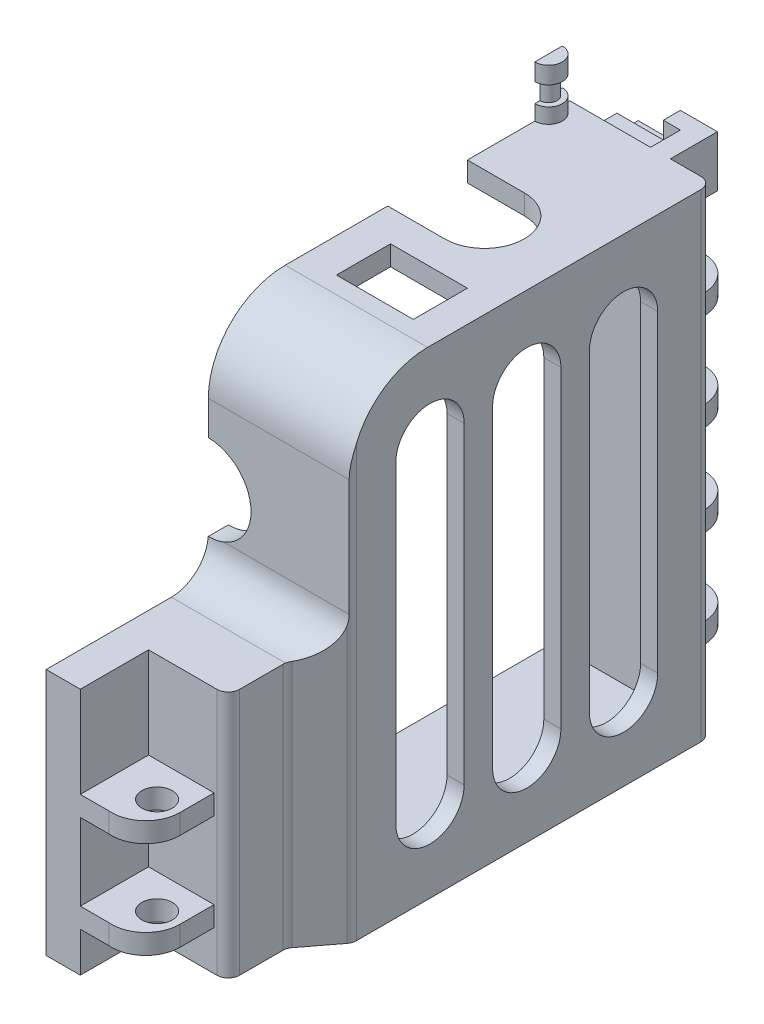
SolidWorks part; units mm, degrees
other "Marca1"
sketch "Croquis36" plane through (80, 81, -87.96) normal (0.1619, 0.9849, -0.0617) x (0.0148, -0.0649, -0.9978)
ref_plane "Front Plane" through (0, 0, 0) normal (0, 0, 1) x (1, 0, 0)
ref_plane "Top Plane" through (0, 0, 0) normal (0, 1, 0) x (1, 0, 0)
ref_plane "Right Plane" through (0, 0, 0) normal (1, 0, 0) x (0, 0, -1)
sketch "Croquis13" plane through (0, 0, 0) normal (0, 1, 0) x (1, 0, 0)
  line L0 (0, 80) -> (23, 80)
  line L1 (25, 78) -> (25, 17.5)
  line L2 (24.5908, 16.2879) -> (20.4092, 10.7997)
  line L3 (20, 9.5876) -> (20, 2)
  line L4 (18, 0) -> (0, 0)
  line L5 (0, 77) -> (22, 77)
  line L6 (22, 77) -> (22, 17.8376)
  line L7 (22, 17.8376) -> (18.0229, 12.6179)
  line L8 (17, 9.5876) -> (17, 3)
  line L9 (17, 3) -> (0, 3)
  line L10 (0, 80) -> (0, 77)
  line L11 (0, 3) -> (0, 0)
  line L12 (0, 77) -> (0, 3)
  line L13 (22, 20) -> (25, 20)
  arc A0 (20, 2) -> (18, 0) centre (18, 2) cw
  arc A1 (20.4092, 10.7997) -> (20, 9.5876) centre (22, 9.5876) ccw
  arc A2 (25, 17.5) -> (24.5908, 16.2879) centre (23, 17.5) cw
  arc A3 (23, 80) -> (25, 78) centre (23, 78) cw
  arc A4 (22, 77) -> (22, 77) centre (22, 77) cw
  arc A5 (22, 17.8376) -> (22, 17.8376) centre (22, 17.8376) cw
  arc A6 (18.0229, 12.6179) -> (17, 9.5876) centre (22, 9.5876) ccw
  arc A7 (17, 3) -> (17, 3) centre (17, 3) cw
  dimension "D1" = 2
  dimension "D2" = 80
  dimension "D3" = 25
  dimension "D4" = 60
  dimension "D5" = 8.25
  dimension "D6" = 20
  dimension "D8" = 2.5
  dimension "D7" = 3
extrude "Saliente-Extruir1" add sketch "Croquis13" along normal blind 3 contours A7 L8 A6 L7 A5 L6 A4 L5 L12 L9 region at (10.6798, 0, -41.1375)
extrude "Saliente-Extruir2" add sketch "Croquis13<3>" along normal blind 80.5 contours L5 A4 L6 L13 L1 A3 L0 L10 region at (11.5, 0, -79.35)
sketch "Croquis13<3>" plane through (0, 0, 0) normal (0, 1, 0) x (1, 0, 0) same geometry as "Croquis13"
extrude "Saliente-Extruir3" add sketch "Croquis13<4>" along normal blind 40 contours L8 A7 L9 L11 L4 A0 L3 A1 L2 A2 L1 L13 L6 A5 L7 A6 region at (8.5, 0, -2.6798)
sketch "Croquis13<4>" plane through (0, 0, 0) normal (0, 1, 0) x (1, 0, 0) same geometry as "Croquis13"
fillet "Redondeo1" radius 10 2 edges at (23.5, 80.5, -20) (23.5, 40, -20)
sketch "Croquis14" plane through (0, 0, 0) normal (1, 0, 0) x (0, 0, -1)
  line L2 (2, 40) -> (0, 40) construction
  line L43 (2, 40) -> (0, 40)
  line L44 (9.5876, 40) -> (2, 40) construction
  line L45 (9.5876, 40) -> (2, 40)
  line L46 (20, 70.5) -> (20, 50) construction
  line L47 (10, 40) -> (9.5876, 40) construction
  line L48 (20, 70.5) -> (20, 50)
  line L49 (10, 40) -> (9.5876, 40)
  line L50 (78, 80.5) -> (30, 80.5) construction
  line L51 (78, 80.5) -> (30, 80.5)
  line L52 (80, 80.5) -> (78, 80.5) construction
  line L53 (80, 80.5) -> (78, 80.5)
  line L54 (80, 84) -> (78, 84)
  line L55 (78, 84) -> (30, 84)
  line L56 (16.5, 70.5) -> (16.5, 50)
  line L57 (10, 43.5) -> (9.5876, 43.5)
  line L58 (9.5876, 43.5) -> (2, 43.5)
  line L59 (2, 43.5) -> (0, 43.5)
  line L60 (0, 43.5) -> (0, 40)
  line L61 (80, 84) -> (80, 80.5)
  arc A24 (17.5, 43.3856) -> (20, 50) centre (10, 50) ccw construction
  arc A25 (16.2879, 42.2242) -> (17.5, 43.3856) centre (10, 50) ccw construction
  arc A26 (10.7997, 40.032) -> (16.2879, 42.2242) centre (10, 50) ccw construction
  arc A27 (10, 40) -> (10.7997, 40.032) centre (10, 50) ccw construction
  arc A28 (17.5, 43.3856) -> (20, 50) centre (10, 50) ccw
  arc A29 (16.2879, 42.2242) -> (17.5, 43.3856) centre (10, 50) ccw
  arc A30 (10.7997, 40.032) -> (16.2879, 42.2242) centre (10, 50) ccw
  arc A31 (10, 40) -> (10.7997, 40.032) centre (10, 50) ccw
  arc A32 (30, 80.5) -> (20, 70.5) centre (30, 70.5) ccw construction
  arc A33 (30, 80.5) -> (20, 70.5) centre (30, 70.5) ccw
  arc A34 (30, 84) -> (16.5, 70.5) centre (30, 70.5) ccw
  arc A35 (14.875, 45.7007) -> (16.5, 50) centre (10, 50) ccw
  arc A36 (14.0871, 44.9458) -> (14.875, 45.7007) centre (10, 50) ccw
  arc A37 (10.5198, 43.5208) -> (14.0871, 44.9458) centre (10, 50) ccw
  arc A38 (10, 43.5) -> (10.5198, 43.5208) centre (10, 50) ccw
  dimension "D1" = 3.5
extrude "Saliente-Extruir4" add sketch "Croquis14" along normal up to surface (25 mm away) up to face at (25, 46.6755, -37.0762)
sketch "Croquis16" plane through (0, 0, 0) normal (1, 0, 0) x (0, 0, -1)
  line L0 (77, 3) -> (61.19, 3) construction
  line L1 (77, 3) -> (3, 3) construction
  line L2 (61.19, 3) -> (56.19, 3) construction
  line L3 (58.69, 3) -> (58.69, 19) construction
  line L4 (61.19, 3) -> (78.15, 3)
  line L5 (61.19, 3) -> (61.19, 19)
  line L6 (61.19, 19) -> (78.15, 19)
  line L7 (78.15, 3) -> (78.15, 19)
  line L8 (61.19, 19) -> (58.69, 19) construction
  line L9 (56.19, 3) -> (53.19, 3)
  line L12 (56.19, 3) -> (56.19, 19)
  line L13 (56.19, 19) -> (56.19, 80.5)
  line L15 (56.19, 19) -> (56.19, 3)
  line L16 (56.19, 3) -> (53.19, 3)
  line L17 (53.19, 80.5) -> (53.19, 3)
  line L18 (30, 80.5) -> (77, 80.5) construction
  line L19 (56.19, 80.5) -> (53.19, 80.5)
  dimension "D1" = 15.81
  dimension "D2" = 5
  dimension "D3" = 16.96
  dimension "D4" = 16
  dimension "D5" = 3
extrude "Saliente-Extruir5" add sketch "Croquis16" along normal up to surface (22 mm away) region at (0, 41.75, -54.69)
sketch "Croquis18" plane through (0, 0, 0) normal (1, 0, 0) x (0, 0, -1)
  line L34 (45.7, 80.5) -> (42.4, 80.5)
  line L35 (45.7, 80.5) -> (45.7, 29.9)
  line L36 (42.4, 68.7) -> (42.4, 36.7)
  line L37 (36.9, 68.7) -> (36.9, 65.5)
  line L38 (77, 80.5) -> (73.7, 80.5)
  line L39 (33.9, 29.9) -> (33.9, 39.9)
  line L40 (42.4, 36.7) -> (36.9, 36.7)
  line L41 (36.9, 36.7) -> (36.9, 39.9)
  line L42 (36.9, 39.9) -> (33.9, 39.9)
  line L43 (36.9, 65.5) -> (33.9, 65.5)
  line L44 (33.9, 65.5) -> (33.9, 80.5)
  line L45 (33.9, 80.5) -> (42.4, 80.5)
  line L46 (36.9, 68.7) -> (42.4, 68.7)
  line L47 (33.9, 29.9) -> (45.7, 29.9)
  line L48 (77, 80.5) -> (77, 29.9)
  line L49 (73.7, 68.7) -> (73.7, 36.7)
  line L50 (68.2, 68.7) -> (68.2, 65.5)
  line L51 (65.2, 29.9) -> (65.2, 39.9)
  line L52 (73.7, 36.7) -> (68.2, 36.7)
  line L53 (68.2, 36.7) -> (68.2, 39.9)
  line L54 (68.2, 39.9) -> (65.2, 39.9)
  line L55 (68.2, 65.5) -> (65.2, 65.5)
  line L56 (65.2, 65.5) -> (65.2, 80.5)
  line L57 (65.2, 80.5) -> (73.7, 80.5)
  line L58 (68.2, 68.7) -> (73.7, 68.7)
  line L59 (65.2, 29.9) -> (77, 29.9)
  line L61 (30, 80.5) -> (53.19, 80.5) construction
  line L62 (77, 80.5) -> (77, 3) construction
  dimension "D1" = 3.3
  dimension "D2" = 10
  dimension "D3" = 5.5
  dimension "D4" = 3.2
  dimension "D5" = 32
  dimension "D6" = 15
  dimension "D7" = 3.3
  dimension "D8" = 3
  dimension "D9" = 5.5
  dimension "D10" = 15
  dimension "D11" = 3.3
  dimension "D13" = 28
sketch "Croquis27" plane through (0, 0, -20) normal (0, 0, 1) x (1, 0, 0)
  circle A0 centre (0, 57) radius 7.5
  dimension "D1" = 57
  dimension "D2" = 15
extrude "Cortar-Extruir4" cut sketch "Croquis27" against normal blind 10 and the other way through all
sketch "Croquis29" plane through (0, 0, 0) normal (-1, 0, 0) x (0, 0, 1)
  line L0 (-53.19, 80.5) -> (-53.19, 3) construction
  line L1 (-56.19, 3) -> (-56.19, 80.5) construction
  line L2 (-53.19, 80.5) -> (-53.19, 3)
  line L3 (-56.19, 3) -> (-56.19, 80.5)
  line L4 (-56.19, 80.5) -> (-53.19, 80.5)
  line L5 (-56.19, 3) -> (-53.19, 3)
extrude "Cortar-Extruir5" cut sketch "Croquis29" against normal up to surface (22 mm away) up to face at (22, 41.75, -66.595)
sketch "Croquis37" plane through (0, 40, 0) normal (0, -1, 0) x (1, 0, 0)
  line L2 (23, -80) -> (25, -80)
  line L3 (20.4092, -10.7997) -> (24.5908, -16.2879)
  line L4 (25, -17.5) -> (25, -10)
  line L5 (25, -10) -> (20.043, -10)
  line L6 (20.4092, -10.7997) -> (24.5908, -16.2879)
  line L7 (25, -17.5) -> (25, -10)
  line L8 (25, -10) -> (20.043, -10)
  line L9 (25, -80) -> (25, -78)
  line L10 (20, -2) -> (20, -9.5876)
  line L11 (20.043, -10) -> (25, -10)
  line L12 (25, -10) -> (25, 0)
  line L13 (25, 0) -> (18, 0)
  line L14 (20, -2) -> (20, -9.5876)
  line L15 (20.043, -10) -> (25, -10)
  line L16 (25, -10) -> (25, 0)
  line L19 (23, -80) -> (25, -80)
  line L20 (25, -80) -> (25, -78)
  line L23 (25, 0) -> (18, 0)
  arc A1 (23, -80) -> (25, -78) centre (23, -78) ccw
  arc A2 (20.043, -10) -> (20.4092, -10.7997) centre (22, -9.5876) ccw
  arc A3 (25, -17.5) -> (24.5908, -16.2879) centre (23, -17.5) ccw
  arc A4 (20.043, -10) -> (20.4092, -10.7997) centre (22, -9.5876) ccw
  arc A5 (25, -17.5) -> (24.5908, -16.2879) centre (23, -17.5) ccw
  arc A6 (20, -2) -> (18, 0) centre (18, -2) ccw
  arc A7 (20, -9.5876) -> (20.043, -10) centre (22, -9.5876) ccw
  arc A8 (20, -2) -> (18, 0) centre (18, -2) ccw
  arc A9 (20, -9.5876) -> (20.043, -10) centre (22, -9.5876) ccw
  arc A10 (23, -80) -> (25, -78) centre (23, -78) ccw
  arc M12 (18, 0) -> (20, -2) centre (18, -2) cw
  line M13 (20, -2) -> (20, -9.5876)
  arc M14 (20, -9.5876) -> (20.043, -10) centre (22, -9.5876) ccw
  line M15 (20.043, -10) -> (25, -10)
  line M16 (25, -10) -> (25, 0)
  line M17 (25, 0) -> (18, 0)
  dimension "D1" = 0
  dimension "D2" = 0
  dimension "D3" = 0
extrude "Cortar-Extruir6" cut sketch "Croquis37" against normal through all contours M17 M12 M13 M14 M15 M16 | A5 L7 A4 L6 M15 | A10 L20 L19 region at (23.2836, 40, -12.2954) region at (22.4505, 40, -4.9226)
sketch "Croquis38" plane through (0, 84, 0) normal (0, 1, 0) x (1, 0, 0)
  line L1 (0, 80) -> (17.65, 80)
  line L2 (0, 80) -> (0, 88.25)
  line L3 (0, 88.25) -> (17.65, 88.25)
  line L4 (17.65, 80) -> (17.65, 88.25)
  line L10 (14.15, 80) -> (14.15, 85.25)
  line L11 (14.15, 85.25) -> (11.15, 85.25)
  line L12 (11.15, 85.25) -> (11.15, 88.25)
  line L13 (0, 80) -> (0, 30) construction
  circle A1 centre (0, 76.25) radius 2.42
  line M6 (23, 80) -> (0, 80)
  line M7 (0, 80) -> (0, 30)
  dimension "D10" = 4.84
  dimension "D2" = 3.5
  dimension "D6" = 11.15
  dimension "D7" = 14.15
  dimension "D8" = 5.25
  dimension "D9" = 12
extrude "Saliente-Extruir8" add sketch "Croquis38" against normal blind 6 contours L12 L11 L10 L4 L3 M6 region at (15.1277, 84, -84.7488)
extrude "Saliente-Extruir9" add sketch "Croquis38<3>" against normal blind 3 from surface contours L12 L11 L10 L4 L3 M6 | L11 L12 L3 L2 L1 L10 region at (6.6093, 84, -83.9057) region at (15.1277, 84, -84.7488) starting at face at (14.3167, 78, -84.5)
sketch "Croquis38<3>" plane through (0, 84, 0) normal (0, 1, 0) x (1, 0, 0) same geometry as "Croquis38"
extrude "Saliente-Extruir10" add sketch "Croquis38<4>" along normal blind 9 contours A1 M7 region at (1.0271, 84, -76.25)
sketch "Croquis38<4>" plane through (0, 84, 0) normal (0, 1, 0) x (1, 0, 0) same geometry as "Croquis38"
sketch "Croquis39" plane through (0, 93, 0) normal (0, 1, 0) x (1, 0, 0)
  line L0 (0, 78.67) -> (0, 73.83) construction
  circle A0 centre (0, 76.25) radius 1.5
  circle A1 centre (0, 76.25) radius 2.42
  dimension "D1" = 3
extrude "Cortar-Extruir7" cut sketch "Croquis39" against normal blind 3.35 from offset 3 offset against normal yes
sketch "Croquis41" plane through (0, 0, 0) normal (0, -1, 0) x (1, 0, 0)
  line L0 (17.5, 6) -> (17.5, 0) construction
  line L1 (6, 11.9791) -> (11, 11.9791)
  line L2 (17.5, 0) -> (6, 0)
  line L3 (6, 0) -> (6, 11.9791)
  line L4 (17.5, 6) -> (17.5, 0)
  line L5 (0, -80) -> (0, 0) construction
  line L6 (0, -40) -> (25, -40) construction
  line L7 (25, -78) -> (25, -17.5) construction
  line L8 (6, -80) -> (6, -91.9791)
  line L9 (17.5, -80) -> (6, -80)
  line L10 (17.5, -86) -> (17.5, -80)
  line L11 (6, -91.9791) -> (11, -91.9791)
  line L12 (0, -91.9791) -> (6, -91.9791)
  line L13 (0, 0) -> (6, 0)
  line L14 (0, 0) -> (0, 11.9791)
  line L15 (0, 11.9791) -> (6, 11.9791)
  line L16 (6, 0) -> (6, 11.9791)
  line L17 (6, -80) -> (6, -91.9791)
  line L18 (0, -80) -> (6, -80)
  line L19 (0, -80) -> (0, -91.9791)
  arc A0 (11, 11.9791) -> (17.5, 6) centre (11.5, 6) cw
  arc A1 (11, -91.9791) -> (17.5, -86) centre (11.5, -86) ccw
  circle A3 centre (13.5, 6) radius 2.675
  circle A4 centre (13.5, -86) radius 2.675
  line M7 (18, 0) -> (0, 0)
  line M9 (0, -80) -> (23, -80)
  dimension "D4" = 6
  dimension "D7" = 5.35
  dimension "D1" = 5
  dimension "D2" = 6
  dimension "D3" = 11.5
  dimension "D5" = 6
  dimension "D8" = 4
extrude "Saliente-Extruir13" add sketch "Croquis41<5>" against normal up to surface (43.5 mm away) contours L15 L14 L3 M7 region at (3, 0, 5.9896) up to face at (13.0744, 43.5, -5.1957)
sketch "Croquis41<5>" plane through (0, 0, 0) normal (0, -1, 0) x (1, 0, 0) same geometry as "Croquis41"
extrude "Saliente-Extruir14" add sketch "Croquis41<6>" against normal up to surface (75 mm away) contours L19 L12 L8 M9 region at (3, 0, -85.9896) up to face at (8.825, 75, -84.125)
sketch "Croquis41<6>" plane through (0, 0, 0) normal (0, -1, 0) x (1, 0, 0) same geometry as "Croquis41"
extrude "Saliente-Extruir11" add sketch "Croquis41" against normal blind 3.5 from offset 7 contours A0 L1 L3 L4 M7 | L11 A1 L10 L8 M9 region at (8.5, 0, 11.8129) region at (11.75, 0, -80.1662) offset against normal yes
extrude "Saliente-Extruir12" add sketch "Croquis41<3>" against normal blind 3.5 from offset 24 contours A0 L1 L3 L4 M7 | L11 A1 L10 L8 M9 region at (8.5, 0, 11.8129) region at (11.75, 0, -80.1662) offset against normal yes
sketch "Croquis41<3>" plane through (0, 0, 0) normal (0, -1, 0) x (1, 0, 0) same geometry as "Croquis41"
extrude "Saliente-Extruir15" add sketch "Croquis41<7>" against normal blind 3.5 from offset 40 contours L11 A1 L10 L8 A4 M9 region at (11.75, 0, -80.1662) offset against normal yes
sketch "Croquis41<7>" plane through (0, 0, 0) normal (0, -1, 0) x (1, 0, 0) same geometry as "Croquis41"
extrude "Saliente-Extruir16" add sketch "Croquis41<8>" against normal blind 3.5 from offset 57 contours L11 A1 L10 L8 A4 M9 region at (11.75, 0, -80.1662) offset against normal yes
sketch "Croquis41<8>" plane through (0, 0, 0) normal (0, -1, 0) x (1, 0, 0) same geometry as "Croquis41"
sketch "Croquis42" plane through (22, 0, 0) normal (-1, 0, 0) x (0, 0, 1)
  line L0 (-47.4188, 69.25) -> (-47.4188, 14.25) construction
  line L1 (-41.4188, 69.25) -> (-41.4188, 14.25)
  line L2 (-53.4188, 69.25) -> (-53.4188, 14.25)
  line L3 (-64.4188, 69.25) -> (-64.4188, 14.25) construction
  line L4 (-58.4188, 69.25) -> (-58.4188, 14.25)
  line L5 (-70.4188, 69.25) -> (-70.4188, 14.25)
  line L6 (-30.4188, 69.25) -> (-30.4188, 14.25) construction
  line L7 (-24.4188, 69.25) -> (-24.4188, 14.25)
  line L8 (-36.4188, 69.25) -> (-36.4188, 14.25)
  line L9 (-77, 3) -> (-17.8376, 3) construction
  line L11 (-77, 80.5) -> (-77, 3) construction
  arc A0 (-41.4188, 69.25) -> (-53.4188, 69.25) centre (-47.4188, 69.25) ccw
  arc A1 (-53.4188, 14.25) -> (-41.4188, 14.25) centre (-47.4188, 14.25) ccw
  arc A2 (-58.4188, 69.25) -> (-70.4188, 69.25) centre (-64.4188, 69.25) ccw
  arc A3 (-70.4188, 14.25) -> (-58.4188, 14.25) centre (-64.4188, 14.25) ccw
  arc A4 (-24.4188, 69.25) -> (-36.4188, 69.25) centre (-30.4188, 69.25) ccw
  arc A5 (-36.4188, 14.25) -> (-24.4188, 14.25) centre (-30.4188, 14.25) ccw
  point P2 (-47.4188, 41.75)
  point P9 (-64.4188, 41.75)
  point P16 (-30.4188, 41.75)
  point P24 (-47.4188, 3)
  point P31 (-77, 41.75)
  dimension "D1" = 6
  dimension "D2" = 5
  dimension "D3" = 5
  dimension "D4" = 55
extrude "Cortar-Extruir8" cut sketch "Croquis42" against normal through all
sketch "Croquis43" plane through (0, 84, 0) normal (0, 1, 0) x (1, 0, 0)
  line L0 (0, 73.83) -> (0, 30) construction
  line L1 (6, 42.5) -> (19.5, 42.5)
  line L2 (6, 42.5) -> (6, 33)
  line L3 (6, 33) -> (19.5, 33)
  line L4 (19.5, 42.5) -> (19.5, 33)
  line L5 (14.15, 80) -> (0, 80) construction
  line L6 (-10, 55) -> (10, 55) construction
  line L7 (-10, 62) -> (10, 62)
  line L8 (-10, 48) -> (10, 48)
  arc A0 (-10, 62) -> (-10, 48) centre (-10, 55) ccw
  arc A1 (10, 48) -> (10, 62) centre (10, 55) ccw
  point P10 (0, 55)
  point P15 (0, 0)
  dimension "D5" = 7
  dimension "D1" = 9.5
  dimension "D2" = 13.5
  dimension "D3" = 6
  dimension "D4" = 37.5
  dimension "D6" = 20
  dimension "D7" = 55
extrude "Cortar-Extruir9" cut sketch "Croquis43" against normal up to next
